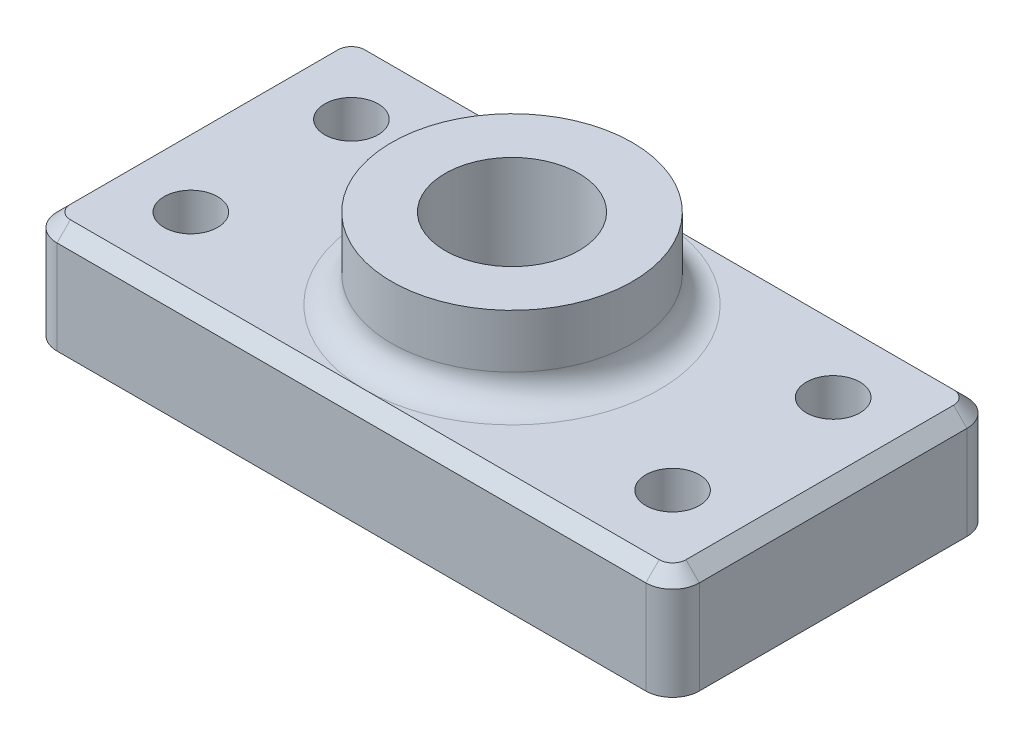
SolidWorks part; units mm, degrees
ref_plane "Front Plane" through (0, 0, 0) normal (0, 0, 1) x (1, 0, 0)
ref_plane "Top Plane" through (0, 0, 0) normal (0, 1, 0) x (1, 0, 0)
ref_plane "Right Plane" through (0, 0, 0) normal (1, 0, 0) x (0, 0, -1)
sketch "Sketch1" plane through (0, 0, 0) normal (0, 1, 0) x (1, 0, 0)
  line L1 (0, 0) -> (152.4, 0)
  line L2 (0, 0) -> (0, 76.2)
  line L3 (0, 76.2) -> (152.4, 76.2)
  line L4 (152.4, 0) -> (152.4, 76.2)
  dimension "D1" = 76.2
  dimension "D2" = 152.4
extrude "Boss-Extrude1" add sketch "Sketch1" along normal blind 25.4
fillet "Fillet1" radius 6.35 4 edges at (0, 12.7, -76.2) (152.4, 12.7, -76.2) (152.4, 12.7, 0) (0, 12.7, 0)
chamfer "Chamfer1" distance 3.175 angle 45 8 edges at (0, 25.4, -38.1) (1.8599, 25.4, -1.8599) (1.8599, 25.4, -74.3401) (76.2, 25.4, 0) (76.2, 25.4, -76.2) (150.5401, 25.4, -1.8599) (150.5401, 25.4, -74.3401) (152.4, 25.4, -38.1)
sketch "Sketch2" plane through (0, 25.4, 0) normal (0, 1, 0) x (1, 0, 0)
  line L0 (76.2, 3.175) -> (76.2, 73.025) construction
  line L3 (6.35, 3.175) -> (146.05, 3.175) construction
  line L4 (146.05, 73.025) -> (6.35, 73.025) construction
  line L5 (149.225, 38.1) -> (3.175, 38.1) construction
  line L6 (149.225, 6.35) -> (149.225, 69.85) construction
  line L7 (3.175, 69.85) -> (3.175, 6.35) construction
  circle A0 centre (76.2, 38.1) radius 28.575
  dimension "D1" = 57.15
extrude "Boss-Extrude2" add sketch "Sketch2" along normal blind 19.05
sketch "Sketch3" plane through (0, 44.45, 0) normal (0, 1, 0) x (1, 0, 0)
  line L0 (76.2, 38.1) -> (104.775, 38.1) construction
  circle A0 centre (76.2, 38.1) radius 28.575 construction
  circle A1 centre (76.2, 38.1) radius 15.875
  dimension "D1" = 31.75
extrude "Cut-Extrude1" cut sketch "Sketch3" against normal through all
fillet "Fillet2" radius 6.35 1 edges at (76.2, 25.4, -66.675)
sketch "Sketch4" plane through (0, 25.4, 0) normal (0, 1, 0) x (1, 0, 0)
  line L0 (76.2, 3.175) -> (76.2, 73.025) construction
  line L1 (149.225, 38.1) -> (3.175, 38.1) construction
  line L2 (149.225, 6.35) -> (149.225, 69.85) construction
  line L3 (3.175, 69.85) -> (3.175, 6.35) construction
  line L5 (152.4, 69.85) -> (152.4, 6.35) construction
  line L6 (146.05, 0) -> (6.35, 0) construction
  arc A0 (76.2, 73.025) -> (76.2, 3.175) centre (76.2, 38.1) ccw construction
  circle A1 centre (133.35, 19.05) radius 6.35
  circle A2 centre (133.35, 57.15) radius 6.35
  circle A3 centre (19.05, 57.15) radius 6.35
  circle A4 centre (19.05, 19.05) radius 6.35
  point P15 (0, 0)
  point P18 (0, 0)
  dimension "D1" = 12.7
  dimension "D2" = 19.05
  dimension "D3" = 19.05
extrude "Cut-Extrude2" cut sketch "Sketch4" against normal through all contours A3 | A4 | A2 | A1
